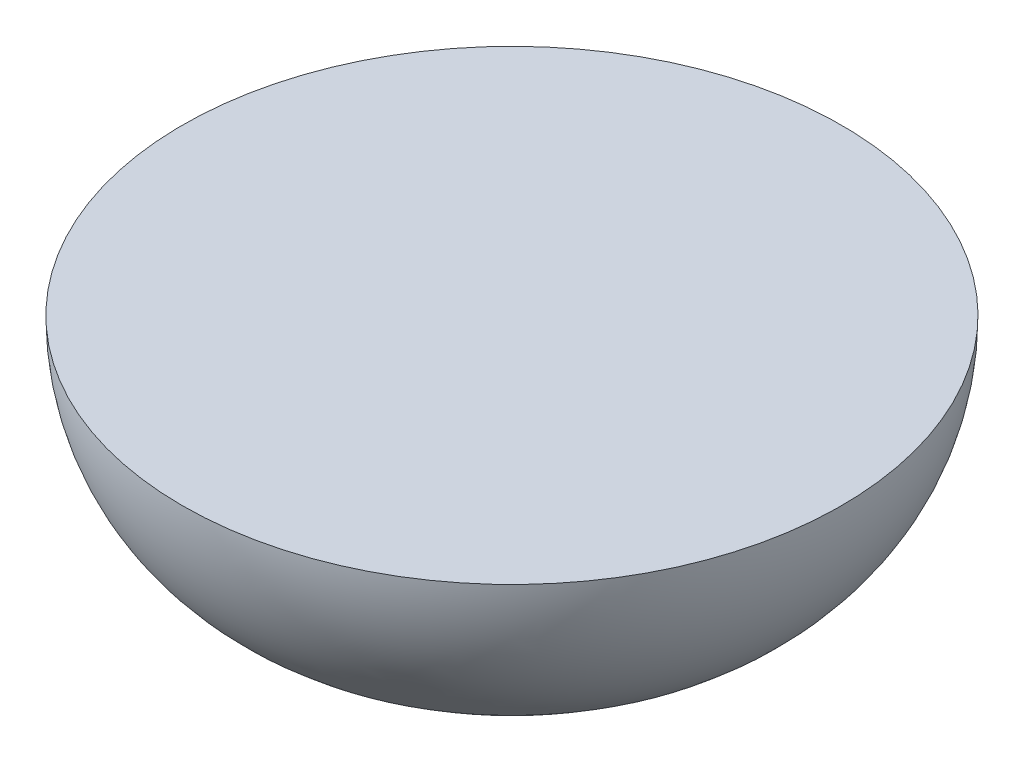
SolidWorks part; units mm, degrees
ref_plane "Спереди" through (0, 0, 0) normal (0, 0, 1) x (1, 0, 0)
ref_plane "Сверху" through (0, 0, 0) normal (0, 1, 0) x (1, 0, 0)
ref_plane "Справа" through (0, 0, 0) normal (1, 0, 0) x (0, 0, -1)
sketch "Sketch1" plane through (0, 0, 0) normal (0, 1, 0) x (1, 0, 0)
  circle A0 centre (0, 0) radius 15
  dimension "D1" = 30
extrude "Boss-Extrude1" add sketch "Sketch1" along normal blind 10
sketch "Sketch2" plane through (0, 0, 0) normal (0, -1, 0) x (1, 0, 0)
  circle A0 centre (0, 0) radius 3.9
  dimension "D1" = 7.8
extrude "Cut-Extrude1" cut sketch "Sketch2" against normal blind 7
fillet "Fillet1" radius 10 1 edges at (0, 0, 15)
